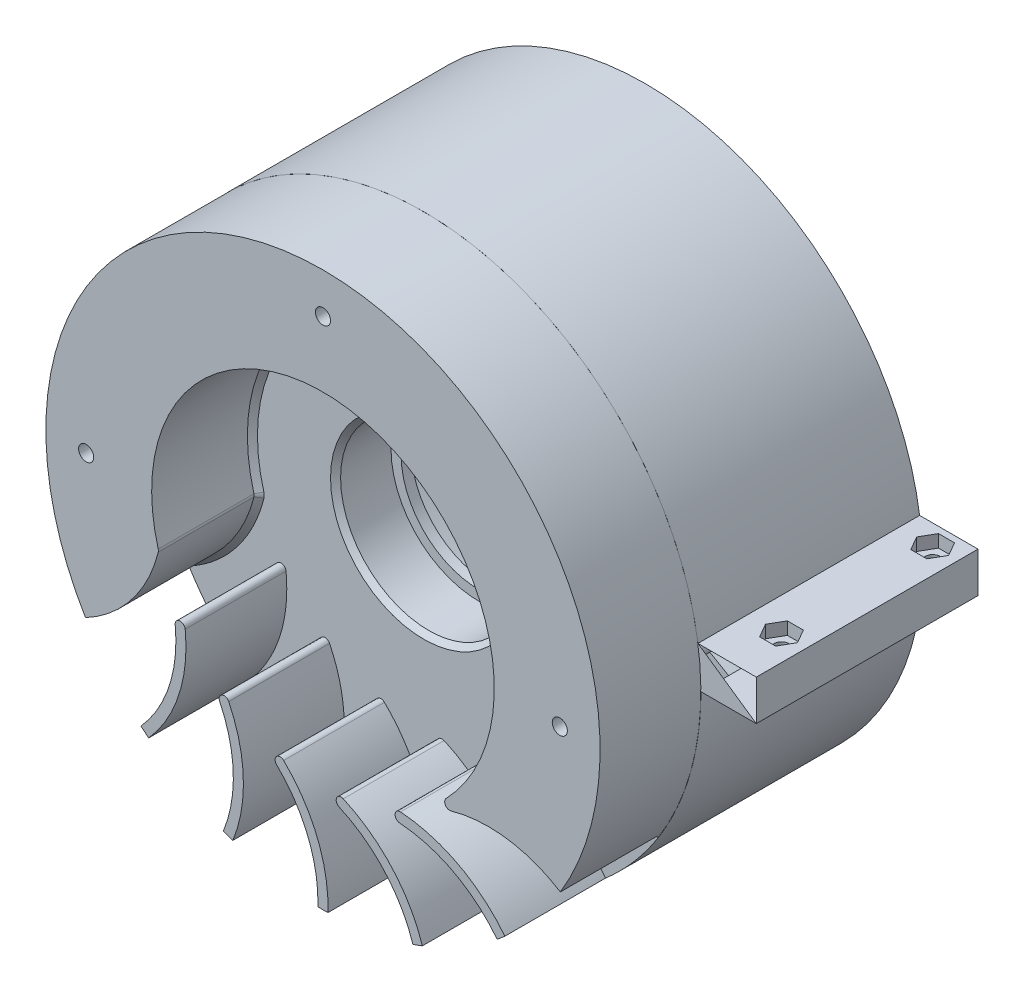
SolidWorks part; units mm, degrees
material "ABS"
ref_plane "前视基准面" through (0, 0, 0) normal (0, 0, 1) x (1, 0, 0)
ref_plane "上视基准面" through (0, 0, 0) normal (0, 1, 0) x (1, 0, 0)
ref_plane "右视基准面" through (0, 0, 0) normal (1, 0, 0) x (0, 0, -1)
other "Configuration Table"
sketch "草图1" plane through (0, 0, 0) normal (1, 0, 0) x (0, 0, -1)
  line L0 (0, 0) -> (32.5576, 0) construction
  line L1 (0, 17.5) -> (44, 17.5)
  line L2 (0, 17.5) -> (0, 55)
  line L3 (0, 55) -> (44, 55)
  line L4 (44, 17.5) -> (44, 55)
  dimension "D1" = 17.5
  dimension "D2" = 55
  dimension "D3" = 44
sketch "草图2" plane through (0, 0, 0) normal (0, 0, 1) x (1, 0, 0)
  line L0 (-33.6531, -9.6161) -> (-22.355, -49.1554) construction
  line L3 (-52.8896, -16.3925) -> (-45.4407, -29.2943) construction
  line L4 (-45.7638, -26.4218) -> (-39.6155, -22.872) construction
  line L5 (0, 0) -> (0, -27.9556) construction
  line L6 (-33.6531, -9.6161) -> (-40.2555, -35.993) construction
  circle A0 centre (0, 0) radius 35 construction
  circle A1 centre (0, 0) radius 54 construction
  arc A4 (-33.6531, -9.6161) -> (-46.7654, -27) centre (-60.7125, -2.8429) cw construction
  arc A5 (-46.2654, -27.866) -> (-32.683, -9.859) centre (-60.7125, -2.8429) ccw
  arc A6 (-47.2654, -26.134) -> (-34.6231, -9.3733) centre (-60.7125, -2.8429) ccw
  arc A7 (-47.2654, -26.134) -> (-46.2654, -27.866) centre (-46.7654, -27) ccw construction
  arc A8 (-32.683, -9.859) -> (-34.6231, -9.3733) centre (-33.6531, -9.6161) ccw
  arc A9 (-47.2654, -26.134) -> (-48.1283, -26.6113) centre (-60.7125, -2.8429) cw
  arc A10 (-54.7677, -5.0001) -> (54.7677, -5.0001) centre (0, 0) ccw construction
  arc A11 (-46.2654, -27.866) -> (-47.1283, -28.3448) centre (-60.7125, -2.8429) cw
  arc A12 (-47.1283, -28.3448) -> (-48.1283, -26.6113) centre (0, 0) cw
  point P6 (-38.4429, -19.6404)
  dimension "D1" = 70
  dimension "D2" = 108
  dimension "D3" = 1
  dimension "D4" = 60
  dimension "D5" = 30
extrude "凸台-拉伸1" add sketch "草图2" along normal blind 20 contours A12 A11 A5 A8 A6 A9 region at (-39.1834, -19.2063, 0)
revolve "旋转1" add sketch "草图1" angle 360 about L0
pattern_circular "阵列(圆周)1" count 7 every 20 about axis through (0, 0, 0) along (0, 0, 1) of "凸台-拉伸1"
sketch "草图3" plane through (0, 0, 0) normal (0, 0, 1) x (1, 0, 0)
  arc A9 (-47.1283, -28.3448) -> (47.1103, -28.3747) centre (0, 0) cw
  arc A20 (-32.6916, -9.3414) -> (24.4357, -23.641) centre (0, 0) cw
  arc A22 (24.8796, -23.3748) -> (25.4291, -25.2979) centre (25.1544, -24.3363) ccw construction
  arc A23 (-47.1283, -28.3448) -> (-32.683, -9.859) centre (-60.7125, -2.8429) ccw construction
  arc A24 (-47.1283, -28.3448) -> (-32.683, -9.859) centre (-60.7125, -2.8429) ccw
  arc A25 (47.1103, -28.3747) -> (25.4291, -25.2979) centre (32.8182, -51.1571) ccw
  arc A26 (-32.683, -9.859) -> (-32.6916, -9.3414) centre (-33.6531, -9.6161) ccw
  arc A27 (24.4357, -23.641) -> (25.4291, -25.2979) centre (25.1544, -24.3363) ccw
  arc A28 (47.1103, -28.3747) -> (25.4291, -25.2979) centre (32.8182, -51.1571) ccw construction
extrude "凸台-拉伸2" add sketch "草图3" along normal up to surface (20 mm away) up to face at (-39.6333, -19.0479, 20)
sketch "草图4" plane through (0, 0, -44) normal (0, 0, -1) x (-1, 0, 0)
  line L0 (-50, 0) -> (-47, 0) construction
  line L1 (-45.25, 3.0311) -> (-49.6863, 5.5924)
  line L2 (-45.25, -3.0311) -> (-49.6863, -5.5924)
  line L3 (3.0311, 45.25) -> (5.5924, 49.6863)
  line L4 (-3.0311, 45.25) -> (-5.5924, 49.6863)
  line L5 (0, 50) -> (0, 47) construction
  line L6 (45.25, -3.0311) -> (49.6863, -5.5924)
  line L7 (45.25, 3.0311) -> (49.6863, 5.5924)
  line L8 (50, 0) -> (47, 0) construction
  line L9 (-3.0311, -45.25) -> (-5.5924, -49.6863)
  line L10 (3.0311, -45.25) -> (5.5924, -49.6863)
  line L11 (0, -50) -> (0, -47) construction
  line L12 (-49.9706, -1.7151) -> (-49.9706, 1.7151) construction
  line L13 (-49.9706, 1.7151) -> (-47, 0) construction
  circle A0 centre (0, 0) radius 50 construction
  circle A1 centre (0, 0) radius 55 construction
  arc A2 (-45.25, -3.0311) -> (-45.25, 3.0311) centre (-47, 0) ccw
  circle A3 centre (-47, 0) radius 1.5
  arc A4 (-49.6863, 5.5924) -> (-35.3553, 35.3553) centre (0, 0) cw
  arc A5 (-49.6863, -5.5924) -> (-31.1791, -39.0879) centre (0, 0) ccw
  arc A6 (-3.0311, 45.25) -> (3.0311, 45.25) centre (0, 47) ccw
  circle A7 centre (0, 47) radius 1.5
  arc A8 (5.5924, 49.6863) -> (35.3553, 35.3553) centre (0, 0) cw
  arc A9 (-5.5924, 49.6863) -> (-39.0879, 31.1791) centre (0, 0) ccw
  arc A10 (45.25, 3.0311) -> (45.25, -3.0311) centre (47, 0) ccw
  circle A11 centre (47, 0) radius 1.5
  arc A12 (49.6863, -5.5924) -> (35.3553, -35.3553) centre (0, 0) cw
  arc A13 (49.6863, 5.5924) -> (31.1791, 39.0879) centre (0, 0) ccw
  arc A14 (3.0311, -45.25) -> (-3.0311, -45.25) centre (0, -47) ccw
  circle A15 centre (0, -47) radius 1.5
  arc A16 (-5.5924, -49.6863) -> (-35.3553, -35.3553) centre (0, 0) cw
  arc A17 (5.5924, -49.6863) -> (39.0879, -31.1791) centre (0, 0) ccw
  point P44 (0, 0)
  circle M8 centre (0, 0) radius 17.5
  dimension "D1" = 5
  dimension "D2" = 3
  dimension "D3" = 2
  dimension "D6" = 45
  dimension "D4" = 30
  dimension "D5" = 30
  dimension "D7" = 45
  dimension "D10" = 60
  dimension "D11" = 47
  dimension "D8" = 4
extrude "切除-拉伸1" cut sketch "草图4" against normal offset from surface (33 mm away) 11 contours L10 A17 A12 L6 A10 L7 A13 A8 L3 A6 L4 A9 A4 L1 A2 L2 A5 A16 L9 A14 M8 | A7 | A11 | A15 | A3 region at (46.7655, 5.5288, -44) region at (47, 0, -44) region at (0, 47, -44) region at (-47, 0, -44) region at (0, -47, -44) up to face at (25.6408, -35.7236, 0)
sketch "草图5" plane through (0, 0, -11) normal (0, 0, -1) x (-1, 0, 0)
  circle A0 centre (-47, 0) radius 1.5 construction
  circle A1 centre (0, 47) radius 1.5
  circle A2 centre (0, 47) radius 1.5
  circle A3 centre (-47, 0) radius 1.5
  circle A6 centre (47, 0) radius 1.5 construction
  circle A7 centre (47, 0) radius 1.5
  dimension "D1" = 0
extrude "切除-拉伸2" cut sketch "草图5" against normal up to surface (31 mm away) up to face at (-0.2385, 1.394, 20)
sketch "草图7" plane through (0, 0, -11) normal (0, 0, -1) x (-1, 0, 0)
  circle A10 centre (0, 0) radius 19.5
  circle A11 centre (0, 0) radius 19.5
  circle A12 centre (0, 0) radius 15.5
  circle A13 centre (0, 0) radius 15.5
  dimension "D1" = 2
  dimension "D2" = 2
extrude "凸台-拉伸3" add sketch "草图7" along normal blind 2
chamfer "倒角2" distance 1 angle 45 1 edges at (17.5, 0, 0)
chamfer "倒角3" distance 1 angle 45 4 edges at (-37.9451, -20.6339, 0) (-32.6532, -9.5996, 0) (24.2967, -24.8506, 0) (8.2559, 32.9824, 0)
sketch "草图9" plane through (0, 0, 0) normal (0, 1, 0) x (1, 0, 0)
  line L0 (-55, 44) -> (-55, 0) construction
  line L11 (-55, 44) -> (-55, 0)
  line L12 (-55, 44) -> (-66, 44)
  line L13 (-66, 44) -> (-66, 0)
  line L14 (-66, 0) -> (-55, 0)
  line L15 (0, -55) -> (0, 55) construction
  line L16 (66, 44) -> (66, 0)
  line L17 (55, 44) -> (66, 44)
  line L18 (55, 44) -> (55, 0)
  line L19 (66, 0) -> (55, 0)
  dimension "D1" = 11
extrude "凸台-拉伸4" add sketch "草图9" along normal blind 8
sketch "草图12" plane through (-55, 0, 0) normal (1, 0, 0) x (0, 0, -1)
  line L4 (0, 0) -> (44, 0)
  line L5 (44, 0) -> (44, 8)
  line L6 (44, 8) -> (0, 8)
  line L7 (0, 8) -> (0, 0)
  line L8 (0, 0) -> (44, 0)
  line L9 (44, 0) -> (44, 8)
  line L10 (44, 8) -> (0, 8)
  line L11 (0, 8) -> (0, 0)
  dimension "D1" = 0
extrude "凸台-拉伸6" add sketch "草图12" along normal up to next
sketch "草图14" plane through (0, 0, 0) normal (0, -1, 0) x (1, 0, 0)
  line L0 (-61, -10) -> (-61, -40) construction
  line L1 (0, -55) -> (0, 55) construction
  line L4 (-66, -44) -> (-55, -44)
  line L5 (-55, -44) -> (-55, 0)
  line L6 (-55, 0) -> (-66, 0)
  line L7 (-66, 0) -> (-66, -44)
  line L8 (-66, -44) -> (-55, -44) construction
  line L10 (-55, 0) -> (-66, 0) construction
  line L11 (-66, 0) -> (-66, -44) construction
  line L13 (-55, -44) -> (-55, 0)
  circle A0 centre (-61, -10) radius 1.5
  circle A1 centre (-61, -40) radius 1.5
  circle A2 centre (61, -40) radius 1.5
  circle A3 centre (61, -10) radius 1.5
  dimension "D2" = 3
  dimension "D5" = 3
  dimension "D3" = 10
  dimension "D4" = 6
  dimension "D6" = 30
  dimension "D1" = 0
extrude "切除-拉伸3" cut sketch "草图14" against normal up to next contours A1 | A0 | A1 | A3 | A2 region at (-61, 0, -40)
sketch "草图15" plane through (55, 0, 0) normal (-1, 0, 0) x (0, 0, 1)
  line L4 (-44, 0) -> (0, 0)
  line L5 (0, 0) -> (0, 8)
  line L6 (0, 8) -> (-44, 8)
  line L7 (-44, 8) -> (-44, 0)
  line L8 (-44, 0) -> (0, 0)
  line L9 (0, 0) -> (0, 8)
  line L10 (0, 8) -> (-44, 8)
  line L11 (-44, 8) -> (-44, 0)
  dimension "D1" = 0
extrude "凸台-拉伸7" add sketch "草图15" along normal up to next
sketch "草图17" plane through (0, 0, 0) normal (0, -1, 0) x (1, 0, 0)
  line L0 (-61, -10) -> (-61, -40) construction
  line L1 (-57.8246, -40) -> (-59.4123, -37.25)
  line L2 (-59.4123, -37.25) -> (-62.5877, -37.25)
  line L3 (-62.5877, -37.25) -> (-64.1754, -40)
  line L4 (-66, -44) -> (-55, -44)
  line L5 (-55, -44) -> (-55, 0)
  line L6 (-55, 0) -> (-66, 0)
  line L7 (-66, 0) -> (-66, -44)
  line L8 (-66, -44) -> (-55, -44) construction
  line L9 (-55, -44) -> (-55, 0) construction
  line L10 (-55, 0) -> (-66, 0) construction
  line L11 (-66, 0) -> (-66, -44) construction
  line L12 (-64.1754, -40) -> (-62.5877, -42.75)
  line L13 (-62.5877, -42.75) -> (-59.4123, -42.75)
  line L14 (-59.4123, -42.75) -> (-57.8246, -40)
  line L15 (0, -55) -> (0, 55) construction
  line L16 (-59.4123, -7.25) -> (-62.5877, -7.25)
  line L17 (-62.5877, -7.25) -> (-64.1754, -10)
  line L18 (-64.1754, -10) -> (-62.5877, -12.75)
  line L19 (-62.5877, -12.75) -> (-59.4123, -12.75)
  line L20 (-59.4123, -12.75) -> (-57.8246, -10)
  line L21 (-57.8246, -10) -> (-59.4123, -7.25)
  line L22 (59.4123, -42.75) -> (57.8246, -40)
  line L23 (62.5877, -42.75) -> (59.4123, -42.75)
  line L24 (64.1754, -40) -> (62.5877, -42.75)
  line L25 (62.5877, -37.25) -> (64.1754, -40)
  line L26 (59.4123, -37.25) -> (62.5877, -37.25)
  line L27 (57.8246, -40) -> (59.4123, -37.25)
  line L28 (57.8246, -10) -> (59.4123, -7.25)
  line L29 (59.4123, -12.75) -> (57.8246, -10)
  line L30 (62.5877, -12.75) -> (59.4123, -12.75)
  line L31 (64.1754, -10) -> (62.5877, -12.75)
  line L32 (62.5877, -7.25) -> (64.1754, -10)
  line L33 (59.4123, -7.25) -> (62.5877, -7.25)
  circle A0 centre (-61, -40) radius 1.5 construction
  circle A1 centre (-61, -10) radius 1.5 construction
  circle A2 centre (-61, -40) radius 1.5 construction
  circle A3 centre (-61, -10) radius 1.5 construction
  circle A4 centre (-61, -40) radius 2.75 construction
  circle A5 centre (-61, -10) radius 2.75 construction
  dimension "D2" = 5.5
  dimension "D3" = 5.5
  dimension "D1" = 0
extrude "切除-拉伸4" cut sketch "草图17" along normal blind 2.5 from surface starting at face at (-61, 8, -41.5)
